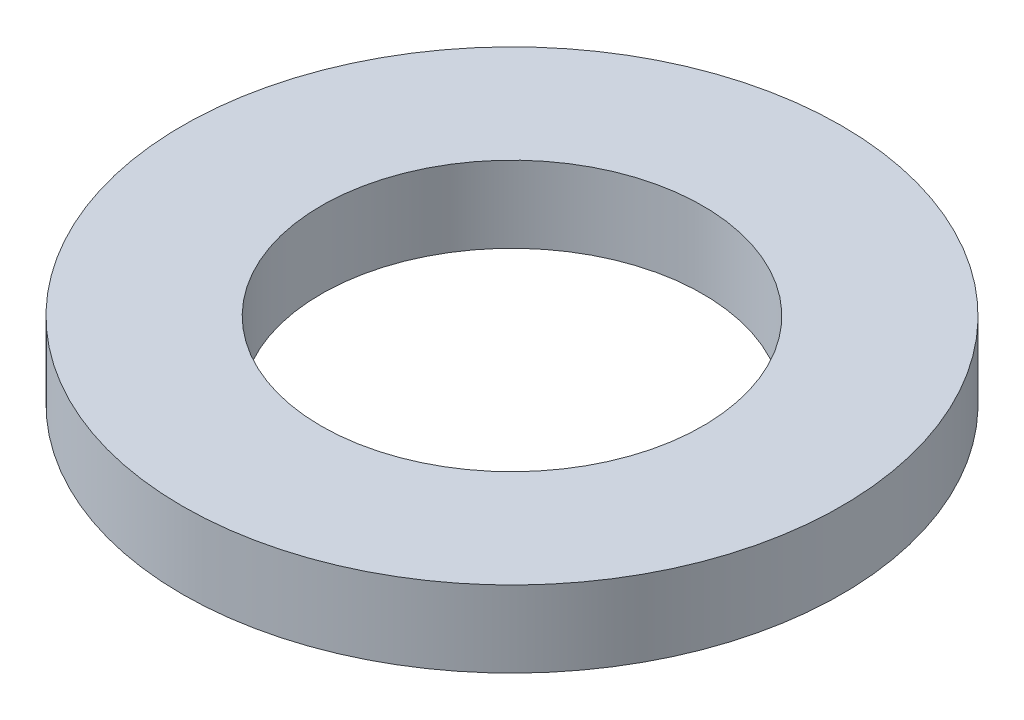
SolidWorks part; units mm, degrees
ref_plane "Front Plane" through (0, 0, 0) normal (0, 0, 1) x (1, 0, 0)
ref_plane "Top Plane" through (0, 0, 0) normal (0, 1, 0) x (1, 0, 0)
ref_plane "Right Plane" through (0, 0, 0) normal (1, 0, 0) x (0, 0, -1)
sketch "Sketch1" plane through (0, 0, 0) normal (0, 1, 0) x (1, 0, 0)
  circle A0 centre (0, 0) radius 47.5
  dimension "FLANGE_OD" = 95
extrude "Boss-Extrude1" add sketch "Sketch1" along normal blind 11
sketch "Sketch2" plane through (0, 0, 0) normal (0, 1, 0) x (1, 0, 0)
  circle A0 centre (0, 0) radius 27.5
  dimension "BORE_D" = 55
extrude "Cut-Extrude1" cut sketch "Sketch2" along normal through all
sketch "Sketch3" plane through (0, 11, 0) normal (0, 1, 0) x (1, 0, 0)
  circle A0 centre (0, 0) radius 17.1127 construction
  circle A1 centre (-17.1127, 0) radius 1.7498
  dimension "BOLT_D" = 3.4997
  dimension "BOLT_PCD" = 34.2254
extrude "Cut-Extrude2" cut sketch "Sketch3" against normal blind 6.8107 rebuild error yes
pattern_circular "CirPattern1" count 4 over 360 rebuild error yes
